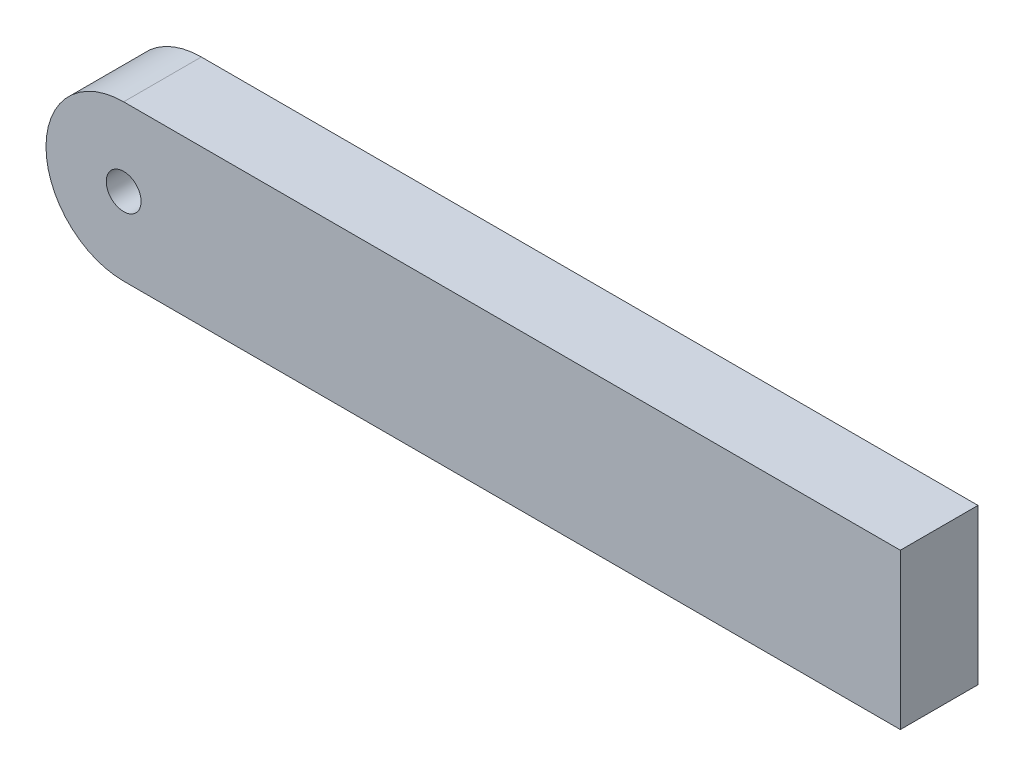
SolidWorks part; units mm, degrees
ref_plane "Front Plane" through (0, 0, 0) normal (0, 0, 1) x (1, 0, 0)
ref_plane "Top Plane" through (0, 0, 0) normal (0, 1, 0) x (1, 0, 0)
ref_plane "Right Plane" through (0, 0, 0) normal (1, 0, 0) x (0, 0, -1)
sketch "Sketch1" plane through (0, 0, 0) normal (0, 1, 0) x (1, 0, 0)
  line L0 (-10, 100) -> (10, 100) construction
  line L2 (10, -100) -> (10, 100)
  line L4 (-10, -100) -> (-10, 100)
  line L5 (10, -100) -> (-10, 100) construction
  line L6 (10, 100) -> (-10, -100) construction
  line L7 (-10, 0) -> (10, 0)
  line L8 (-1.5875, 98.4125) -> (1.5875, 98.4125)
  line L9 (-1.5875, 98.4125) -> (-1.5875, 101.5875)
  line L10 (-1.5875, 101.5875) -> (1.5875, 101.5875)
  line L11 (1.5875, 98.4125) -> (1.5875, 101.5875)
  line L12 (-1.5875, 98.4125) -> (1.5875, 101.5875) construction
  line L13 (-1.5875, 101.5875) -> (1.5875, 98.4125) construction
  arc A0 (-10, 100) -> (10, 100) centre (0, 100) cw
  arc A1 (10, -100) -> (-10, -100) centre (0, -100) cw
  circle A2 centre (0, -100) radius 2.5
  circle A3 centre (0, 100) radius 2.2451
  point P0 (0, 0)
  dimension "D3" = 5
  dimension "D1" = 200
  dimension "D2" = 20
  dimension "D4" = 3.175
extrude "Boss-Extrude1" add sketch "Sketch1" along normal blind 10 contours A1 L2 A0 L4 A3 A2 region at (0, 0, -53.6095)
move or copy body "Body-Move/Copy1" bodies to move or copy 101 copy no rotation origin (-1.6667, 3.3333, -1.6667) rotation axis (0.5774, 0.5774, 0.5774) rotation angle 120
move or copy body "Body-Move/Copy2" bodies to move or copy 102 copy no translate (100, -5, 0)
